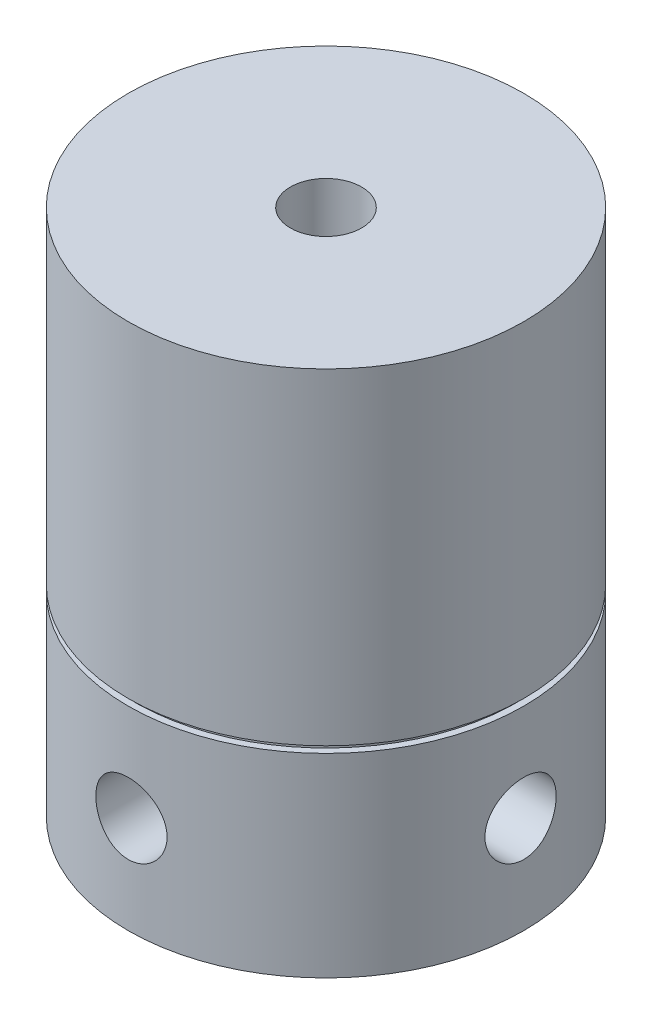
SolidWorks part; units mm, degrees
ref_plane "Front Plane" through (0, 0, 0) normal (0, 0, 1) x (1, 0, 0)
ref_plane "Top Plane" through (0, 0, 0) normal (0, 1, 0) x (1, 0, 0)
ref_plane "Right Plane" through (0, 0, 0) normal (1, 0, 0) x (0, 0, -1)
sketch "Sketch3" plane through (0, 0, 0) normal (0, 0, 1) x (1, 0, 0)
  line L0 (0, 0) -> (38.1, 0)
  line L1 (38.1, 0) -> (38.1, 37.465)
  line L2 (38.1, 37.465) -> (36.83, 37.465)
  line L3 (36.83, 37.465) -> (36.83, 38.735)
  line L4 (36.83, 38.735) -> (38.1, 38.735)
  line L5 (38.1, 38.735) -> (38.1, 101.6)
  line L6 (38.1, 101.6) -> (0, 101.6)
  line L7 (0, 101.6) -> (0, 0)
  line L8 (36.83, 38.1) -> (38.1, 38.1) construction
  point P11 (0, 0)
  point P12 (38.1, 25.3515)
  point P13 (35.5478, 24.4935)
  dimension "D1" = 38.1
  dimension "D2" = 38.1
  dimension "D3" = 101.6
  dimension "D4" = 1.27
  dimension "D5" = 1.27
revolve "Revolve1" add sketch "Sketch3" angle 360 about L7 region at (19.0423, 50.8053, 0)
sketch "Sketch4" plane through (0, 0, 0) normal (0, 0, 1) x (1, 0, 0)
  line L0 (-38.1, 0) -> (38.1, 0) construction
  line L1 (-38.1, 0) -> (38.1, 0)
  line L2 (38.1, 37.465) -> (-38.1, 37.465) construction
  line L3 (38.1, 37.465) -> (-38.1, 37.465)
  line L4 (0, 37.465) -> (0, 0) construction
  circle A0 centre (0, 18.7325) radius 6.858
  dimension "D1" = 13.716
extrude "Cut-Extrude1" cut sketch "Sketch4" against normal through all both and the other way through all contours A0
sketch "Sketch5" plane through (0, 0, 0) normal (1, 0, 0) x (0, 0, -1)
  line L0 (38.1, 37.465) -> (-38.1, 37.465) construction
  line L1 (-38.1, 0) -> (38.1, 0) construction
  line L2 (38.1, 37.465) -> (-38.1, 37.465)
  line L3 (-38.1, 0) -> (38.1, 0)
  line L4 (0, 37.465) -> (0, 0) construction
  circle A0 centre (0, 18.7325) radius 6.858
  circle A1 centre (0, 18.7325) radius 10.668
  dimension "D1" = 13.716
  dimension "D2" = 21.336
extrude "Cut-Extrude2" cut sketch "Sketch5" along normal through all contours A0
extrude "Cut-Extrude3" cut sketch "Sketch5<3>" against normal through all contours A1
sketch "Sketch5<3>" plane through (0, 0, 0) normal (1, 0, 0) x (0, 0, -1) same geometry as "Sketch5"
sketch "Sketch6" plane through (0, 101.6, 0) normal (0, 1, 0) x (1, 0, 0)
  circle A0 centre (0, 0) radius 6.858
  circle A1 centre (0, 0) radius 38.1
  circle A2 centre (0, 0) radius 38.1
  dimension "D2" = 13.716
  dimension "D1" = 0
extrude "Cut-Extrude4" cut sketch "Sketch6" against normal blind 25.4 contours A0 region at (0, 101.6, 0)
